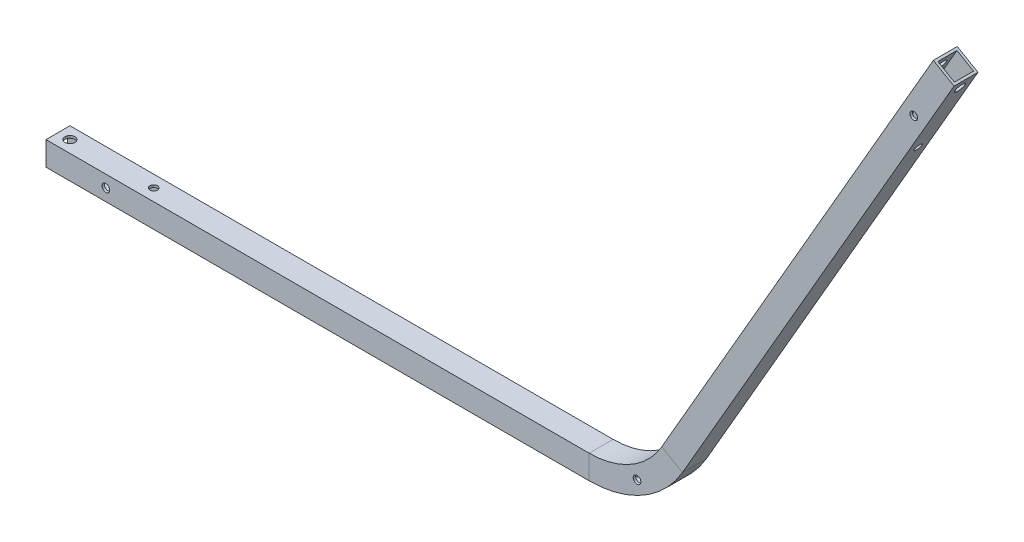
SolidWorks part; units mm, degrees
ref_plane "正面" through (0, 0, 0) normal (0, 0, 1) x (1, 0, 0)
ref_plane "平面" through (0, 0, 0) normal (0, 1, 0) x (1, 0, 0)
ref_plane "右側面" through (0, 0, 0) normal (1, 0, 0) x (0, 0, -1)
sketch "ｽｹｯﾁ2" plane through (0, 0, 0) normal (0, 0, 1) x (1, 0, 0)
  line L0 (0, 0) -> (226.906, 0)
  line L1 (261.547, 20) -> (375, 216.5064)
  arc A0 (226.906, 0) -> (261.547, 20) centre (226.906, 40) ccw
  point P6 (250, 0)
  dimension "D4" = 40
  dimension "D1" = 250
  dimension "D2" = 250
  dimension "D3" = 120
sketch "ｽｹｯﾁ3" plane through (0, 0, 0) normal (1, 0, 0) x (0, 0, -1)
  line L0 (4, -4) -> (4, 4)
  line L1 (5, -5) -> (-5, -5)
  line L2 (5, -5) -> (5, 5)
  line L3 (5, 5) -> (-5, 5)
  line L4 (-5, -5) -> (-5, 5)
  line L5 (5, -5) -> (-5, 5) construction
  line L6 (5, 5) -> (-5, -5) construction
  line L7 (4, 4) -> (-4, 4)
  line L8 (-4, -4) -> (-4, 4)
  line L9 (4, -4) -> (-4, -4)
  point P0 (0, 0)
  dimension "D1" = 10
  dimension "D2" = 10
  dimension "D3" = 1
sweep "ｽｲｰﾌﾟ1" add profiles "ｽｹｯﾁ3" path "ｽｹｯﾁ2"
sketch "ｽｹｯﾁ5" plane through (0, 0, 5) normal (0, 0, 1) x (1, 0, 0)
  line L0 (0, 5) -> (0, -5) construction
  line L1 (370.6699, 219.0064) -> (379.3301, 214.0064) construction
  line L2 (257.2169, 22.5) -> (370.6699, 219.0064) construction
  line L3 (244.406, 9.6891) -> (249.406, 1.0289) construction
  circle A0 centre (25, 0) radius 1.6
  circle A1 centre (362.5, 194.8557) radius 1.6
  arc A4 (226.906, 5) -> (257.2169, 22.5) centre (226.906, 40) ccw construction
  arc A5 (226.906, -5) -> (265.8771, 17.5) centre (226.906, 40) ccw construction
  circle A6 centre (246.906, 5.359) radius 1.6
  dimension "D1" = 25
  dimension "D2" = 3.2
  dimension "D3" = 3.2
  dimension "D4" = 25
  dimension "D5" = 5
  dimension "D6" = 3.2
extrude "ｶｯﾄ - 押し出し2" cut sketch "ｽｹｯﾁ5" against normal blind 10
sketch "ｽｹｯﾁ6" plane through (0, -5, 0) normal (0, -1, 0) x (1, 0, 0)
  line L0 (0, 5) -> (0, -5) construction
  circle A0 centre (5, 0) radius 2.1
  circle A1 centre (40, 0) radius 1.6
  dimension "D1" = 5
  dimension "D2" = 4.2
  dimension "D3" = 35
  dimension "D4" = 3.2
extrude "ｶｯﾄ - 押し出し3" cut sketch "ｽｹｯﾁ6" against normal blind 10
sketch "ｽｹｯﾁ7" plane through (191.8301, -110.7532, 0) normal (0.866, -0.5, 0) x (0, 0, -1)
  line L0 (-5, 375) -> (5, 375) construction
  circle A0 centre (0, 370) radius 2.1
  circle A1 centre (0, 335) radius 1.6
  dimension "D2" = 4.2
  dimension "D3" = 35
  dimension "D4" = 3.2
  dimension "D1" = 5
extrude "ｶｯﾄ - 押し出し4" cut sketch "ｽｹｯﾁ7" against normal blind 10
